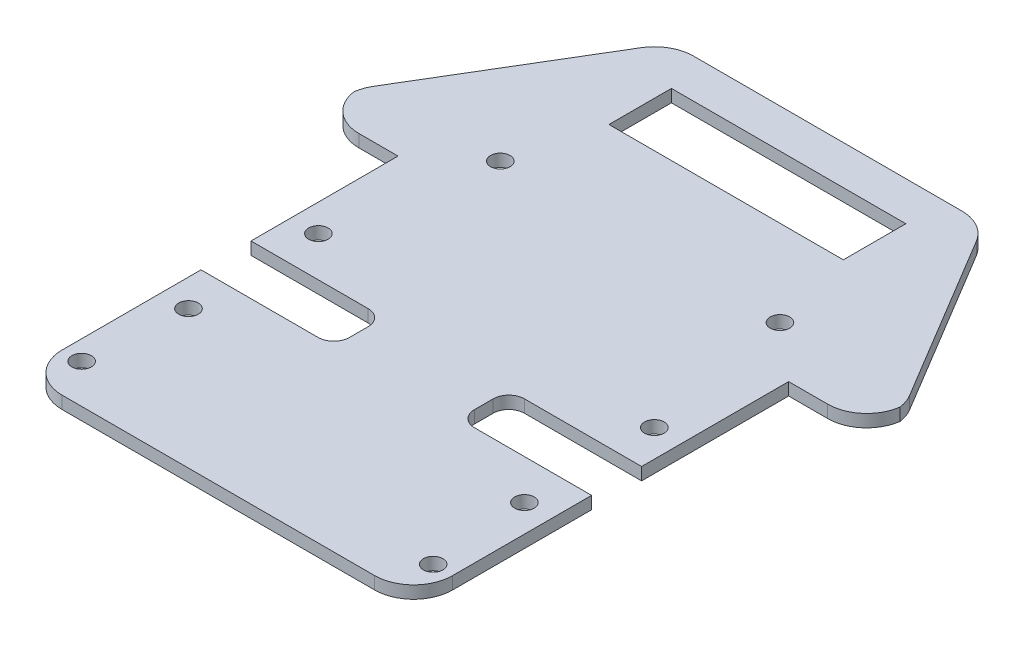
SolidWorks part; units mm, degrees
ref_plane "Front Plane" through (0, 0, 0) normal (0, 0, 1) x (1, 0, 0)
ref_plane "Top Plane" through (0, 0, 0) normal (0, 1, 0) x (1, 0, 0)
ref_plane "Right Plane" through (0, 0, 0) normal (1, 0, 0) x (0, 0, -1)
sketch "Sketch1" plane through (0, 0, 0) normal (0, 1, 0) x (1, 0, 0)
  line L0 (-20, 55.9167) -> (20, 55.9167)
  line L1 (-25, -22.0833) -> (25, -22.0833)
  line L2 (-35, 25.9167) -> (-35, 30.9167)
  line L4 (35, 25.9167) -> (35, 30.9167)
  line L5 (-25, -22.0833) -> (35, 30.9167) construction
  line L6 (-35, 30.9167) -> (25, -22.0833) construction
  line L9 (-35, 25.9167) -> (-25, 25.9167)
  line L10 (-25, -22.0833) -> (-25, 25.9167)
  line L13 (35, 25.9167) -> (25, 25.9167)
  line L14 (25, -22.0833) -> (25, 25.9167)
  line L15 (-20, 55.9167) -> (-35, 30.9167)
  line L16 (20, 55.9167) -> (35, 30.9167)
  point P0 (0, 0)
  point P16 (0, 55.9167)
  dimension "D5" = 30
  dimension "D1" = 50
  dimension "D2" = 10
  dimension "D3" = 48
  dimension "D4" = 5
  dimension "D6" = 40
extrude "Boss-Extrude1" add sketch "Sketch1" along normal blind 1.6
fillet "Fillet1" radius 5 8 edges at (-20, 0.8, -55.9167) (20, 0.8, -55.9167) (-35, 0.8, -30.9167) (35, 0.8, -30.9167) (-25, 0.8, 22.0833) (25, 0.8, 22.0833) (-35, 0.8, -25.9167) (35, 0.8, -25.9167)
sketch "Sketch2" plane through (0, 0, 0) normal (0, 1, 0) x (1, 0, 0)
  line L0 (-20, -22.0833) -> (20, -22.0833) construction
  line L1 (25, -17.0833) -> (25, 25.9167) construction
  line L2 (0, 0) -> (0, -22.0833) construction
  line L3 (25, -17.0833) -> (25, 25.9167) construction
  line L4 (8, 0.6967) -> (25, 0.6967)
  line L5 (8, 0.6967) -> (8, 7.0967)
  line L6 (8, 7.0967) -> (25, 7.0967)
  line L7 (25, 0.6967) -> (25, 7.0967)
  line L8 (8, 0.6967) -> (25, 7.0967) construction
  line L9 (8, 7.0967) -> (25, 0.6967) construction
  line L10 (-8, 7.0967) -> (-25, 7.0967)
  line L11 (-25, 0.6967) -> (-25, 7.0967)
  line L12 (-8, 0.6967) -> (-25, 0.6967)
  line L13 (-8, 0.6967) -> (-8, 7.0967)
  line L14 (17.169, 55.9167) -> (-17.169, 55.9167) construction
  line L15 (15, 50.9167) -> (-15, 50.9167)
  line L16 (15, 50.9167) -> (15, 42.9167)
  line L17 (15, 42.9167) -> (-15, 42.9167)
  line L18 (-15, 50.9167) -> (-15, 42.9167)
  line L19 (15, 50.9167) -> (-15, 42.9167) construction
  line L20 (15, 42.9167) -> (-15, 50.9167) construction
  circle A0 centre (22.5, -17.0833) radius 1.25
  circle A1 centre (21.5, -4.4033) radius 1.25
  circle A2 centre (17.9, 31.9067) radius 1.25
  circle A3 centre (21.5, 12.2267) radius 1.25
  circle A4 centre (-17.9, 31.9067) radius 1.25
  circle A5 centre (-21.5, 12.2267) radius 1.25
  circle A6 centre (-21.5, -4.4033) radius 1.25
  circle A7 centre (-22.5, -17.0833) radius 1.25
  point P23 (16.5, 3.8967)
  point P30 (25, 3.8967)
  point P35 (0, 46.9167)
  point P42 (0, 0)
  dimension "D1" = 16.63
  dimension "D2" = 5
  dimension "D3" = 2.5
  dimension "D4" = 3.5
  dimension "D5" = 12.68
  dimension "D6" = 19.68
  dimension "D7" = 7.1
  dimension "D8" = 2.5
  dimension "D9" = 6.4
  dimension "D10" = 8.3
  dimension "D11" = 17
  dimension "D12" = 8
  dimension "D13" = 30
  dimension "D14" = 5
extrude "Cut-Extrude1" cut sketch "Sketch2" along normal blind 3
fillet "Fillet2" radius 2 4 edges at (8, 0.8, -0.6967) (8, 0.8, -7.0967) (-8, 0.8, -0.6967) (-8, 0.8, -7.0967)
